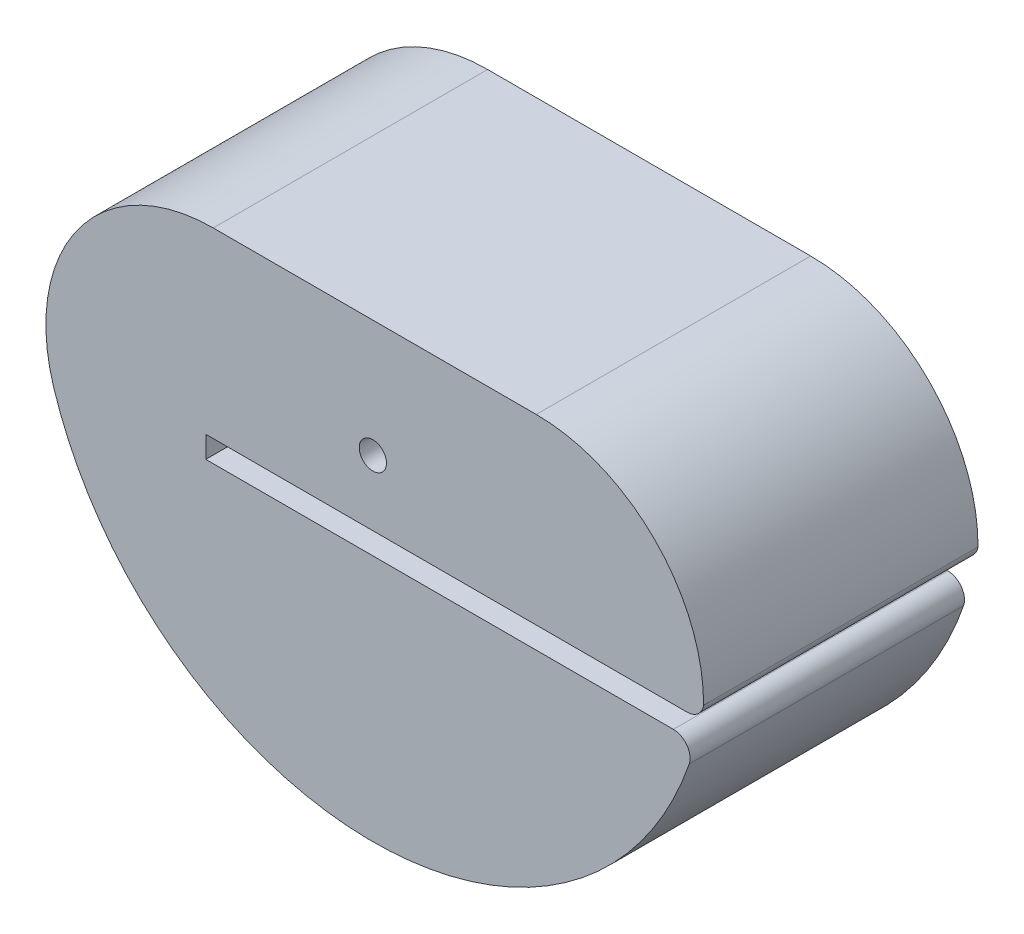
SolidWorks part; units mm, degrees
ref_plane "Front Plane" through (0, 0, 0) normal (0, 0, 1) x (1, 0, 0)
ref_plane "Top Plane" through (0, 0, 0) normal (0, 1, 0) x (1, 0, 0)
ref_plane "Right Plane" through (0, 0, 0) normal (1, 0, 0) x (0, 0, -1)
sketch "Sketch1" plane through (0, 0, 0) normal (0, 0, 1) x (1, 0, 0)
  line L0 (0, -50.8) -> (0, -12.7) construction
  circle A0 centre (0, 0) radius 50.8
  circle A1 centre (0, 0) radius 2.0638
  dimension "D1" = 101.6
  dimension "D2" = 4.1275
  dimension "D3" = 38.1
extrude "Boss-Extrude1" add sketch "Sketch1" along normal blind 41.656
sketch "Sketch2" plane through (0, 0, 0) normal (0, 0, -1) x (-1, 0, 0)
  line L0 (0, -50.8) -> (0, -13.208)
  line L2 (-49.8248, -13.208) -> (25.3592, -13.208)
  line L3 (-49.8248, -13.208) -> (-49.8248, -9.906)
  line L4 (-49.8248, -9.906) -> (25.3592, -9.906)
  line L5 (25.3592, -13.208) -> (25.3592, -9.906)
  line L6 (-47.5869, 17.78) -> (47.5869, 17.78)
  line L7 (-47.5869, 17.78) -> (-47.5869, 66.1039)
  line L8 (-47.5869, 66.1039) -> (47.5869, 66.1039)
  line L9 (47.5869, 17.78) -> (47.5869, 66.1039)
  circle A0 centre (0, 0) radius 50.8 construction
  circle A1 centre (0, 0) radius 2.0638 construction
  dimension "D1" = 37.592
  dimension "D2" = 3.302
  dimension "D3" = 75.184
  dimension "D4" = 66.1039
  dimension "D5" = 17.78
extrude "Cut-Extrude6" cut sketch "Sketch2" against normal blind 76.2 contours L4 L5 L2 L3 | L7 L6 L9 L8
fillet "Fillet1" radius 2.54 2 edges at (49.8248, -9.906, 20.828) (49.0529, -13.208, 20.828)
fillet "Fillet3" radius 25.4 2 edges at (-47.5869, 17.78, 20.828) (47.5869, 17.78, 20.828)
